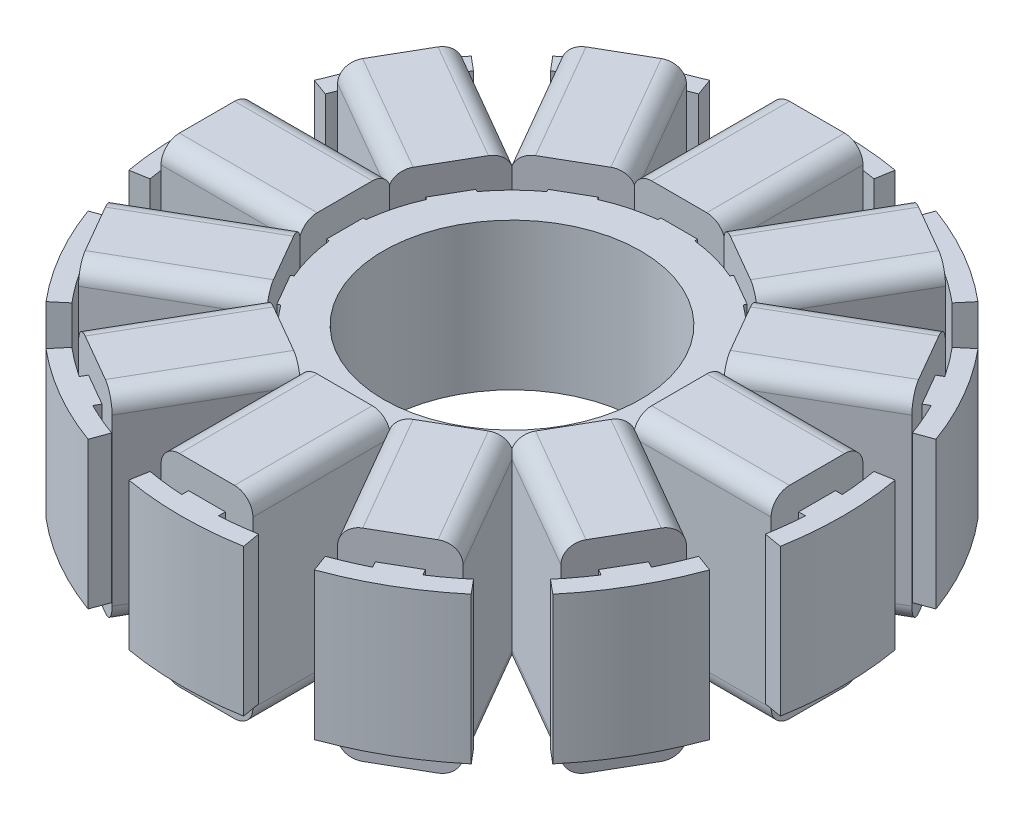
SolidWorks part; units mm, degrees
ref_plane "Front Plane" through (0, 0, 0) normal (0, 0, 1) x (1, 0, 0)
ref_plane "Top Plane" through (0, 0, 0) normal (0, 1, 0) x (1, 0, 0)
ref_plane "Right Plane" through (0, 0, 0) normal (1, 0, 0) x (0, 0, -1)
sketch "Sketch1" plane through (0, 0, 0) normal (0, 1, 0) x (1, 0, 0)
  line L0 (-1, 8.9443) -> (-1, 16.9706)
  line L1 (0, 0) -> (0, 13.6776) construction
  line L2 (1, 8.9443) -> (1, 16.9706)
  line L3 (-3.1257, 17.7265) -> (-2.952, 16.7417)
  line L4 (3.1257, 17.7265) -> (2.952, 16.7417)
  circle A0 centre (0, 0) radius 7
  circle A1 centre (0, 0) radius 9
  arc A2 (2.952, 16.7417) -> (1, 16.9706) centre (0, 0) ccw
  arc A3 (3.1257, 17.7265) -> (-3.1257, 17.7265) centre (0, 0) ccw
  arc A4 (-1, 16.9706) -> (-2.952, 16.7417) centre (0, 0) ccw
  dimension "D1" = 14
  dimension "D2" = 2
  dimension "D3" = 36
  dimension "D4" = 1
  dimension "D5" = 20
  dimension "D6" = 2
extrude "Boss-Extrude1" add sketch "Sketch1" along normal blind 8 contours A0 A1 region at (0, 0, -8.7454)
extrude "Boss-Extrude4" add sketch "Sketch1<3>" along normal blind 8 contours A4 L0 A1 L2 A2 L4 A3 L3 region at (0, 0, -14.2089)
sketch "Sketch1<3>" plane through (0, 0, 0) normal (0, 1, 0) x (1, 0, 0) same geometry as "Sketch1"
ref_plane "Plane1" through (0, 0, -9.1) normal (0, 0, 1) x (1, 0, 0)
sketch "Sketch2" plane through (0, 0, -9.1) normal (0, 0, 1) x (1, 0, 0)
  line L3 (1, 8) -> (-1, 8)
  line L4 (-1, 8) -> (-1, 0)
  line L5 (-1, 8) -> (-1, 0)
  line L8 (-2.5, 8.5) -> (-2.5, -0.5)
  line L9 (1.5, -1.5) -> (-1.5, -1.5)
  line L10 (2.5, 8.5) -> (2.5, -0.5)
  line L11 (1.5, 9.5) -> (-1.5, 9.5)
  line L15 (1, 8) -> (-1, 8)
  line L36 (1, 0) -> (-1, 0)
  line L41 (1, 0) -> (-1, 0)
  line L44 (1, 8) -> (1, 0)
  line L45 (1, 8) -> (1, 0)
  arc A0 (-2.5, -0.5) -> (-1.5, -1.5) centre (-1.5, -0.5) ccw
  arc A1 (1.5, -1.5) -> (2.5, -0.5) centre (1.5, -0.5) ccw
  arc A2 (2.5, 8.5) -> (1.5, 9.5) centre (1.5, 8.5) ccw
  arc A3 (-2.5, 8.5) -> (-1.5, 9.5) centre (-1.5, 8.5) cw
  point P0 (0, 0)
  dimension "D2" = 1
  dimension "D1" = 1.5
  dimension "D3" = 1.5
  dimension "D4" = 1.5
  dimension "D5" = 1.5
extrude "Boss-Extrude5" add sketch "Sketch2" against normal blind 7.5 contours A2 L11 A3 L8 A0 L9 A1 L10
pattern_circular "CirPattern2" count 12 over 360 about axis through (0, 8, 0) along (0, -1, 0) of "Boss-Extrude4"
pattern_circular "CirPattern3" count 12 over 360 of "Boss-Extrude5"
